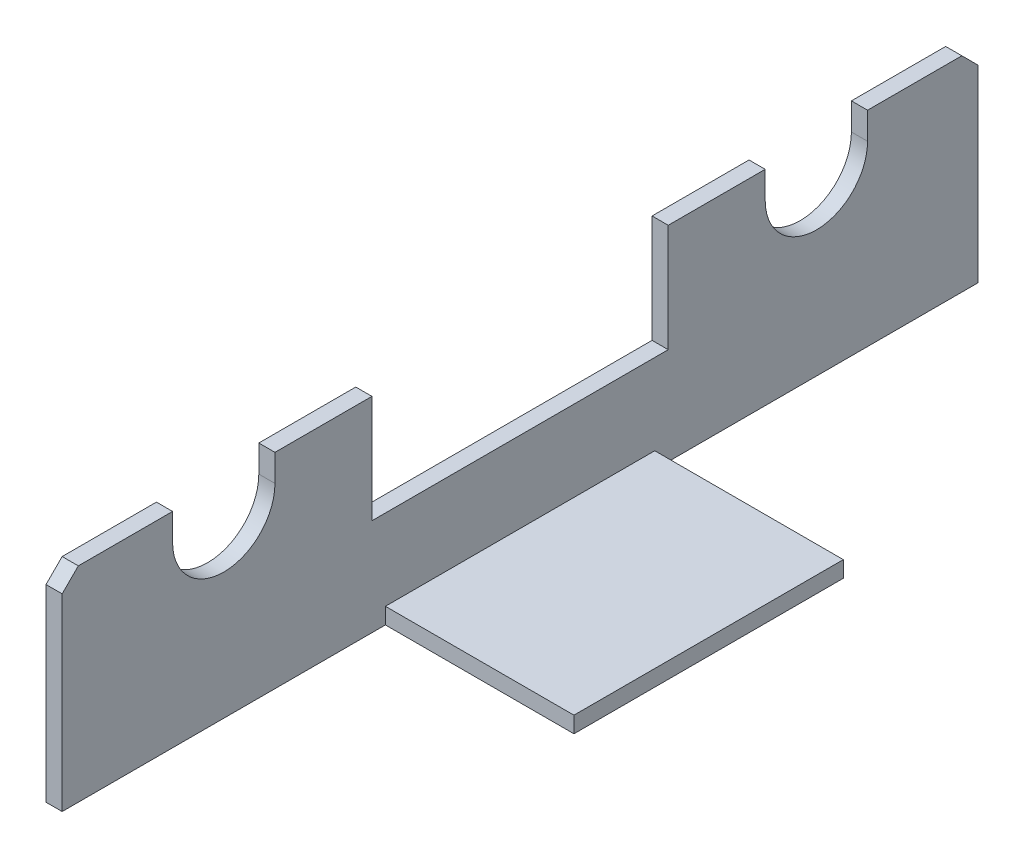
SolidWorks part; units mm, degrees
ref_plane "Alzado" through (0, 0, 0) normal (0, 0, 1) x (1, 0, 0)
ref_plane "Planta" through (0, 0, 0) normal (0, 1, 0) x (1, 0, 0)
ref_plane "Vista lateral" through (0, 0, 0) normal (1, 0, 0) x (0, 0, -1)
sketch "Croquis1" plane through (0, 0, 0) normal (0, 0, 1) x (1, 0, 0)
  line L0 (0, 0) -> (0, 38)
  line L1 (0, 0) -> (38, 0)
  line L2 (3, 3) -> (38, 3)
  line L3 (3, 3) -> (3, 38)
  line L4 (0, 38) -> (3, 38)
  line L5 (38, 3) -> (38, 0)
  dimension "D2" = 38
  dimension "D1" = 3
extrude "Saliente-Extruir1" add sketch "Croquis1" along normal blind 170
sketch "Croquis2" plane through (0, 0, 0) normal (-1, 0, 0) x (0, 0, 1)
  line L0 (170, 33) -> (0, 33) construction
  line L1 (170, 38) -> (170, 0) construction
  line L2 (0, 38) -> (0, 0) construction
  line L3 (170, 3) -> (0, 3) construction
  line L4 (170, 3) -> (0, 3) construction
  line L5 (85, 3) -> (85, 38) construction
  line L6 (170, 38) -> (0, 38) construction
  line L7 (112.5, 18) -> (112.5, 38)
  line L8 (112.5, 58) -> (57.5, 58) construction
  line L9 (112.5, 58) -> (112.5, 18) construction
  line L10 (112.5, 18) -> (57.5, 18)
  line L11 (57.5, 58) -> (57.5, 18) construction
  line L12 (112.5, 58) -> (57.5, 18) construction
  line L13 (112.5, 18) -> (57.5, 58) construction
  line L14 (57.5, 18) -> (57.5, 38)
  line L15 (57.5, 38) -> (112.5, 38)
  line L16 (149.5, 33) -> (149.5, 38)
  line L17 (130.5, 33) -> (130.5, 38)
  line L18 (130.5, 38) -> (149.5, 38)
  line L19 (39.5, 33) -> (39.5, 38)
  line L20 (20.5, 33) -> (20.5, 38)
  line L21 (39.5, 38) -> (20.5, 38)
  circle A0 centre (140, 33) radius 9.5 construction
  circle A1 centre (30, 33) radius 9.5 construction
  arc A2 (149.5, 33) -> (130.5, 33) centre (140, 33) cw
  arc A3 (39.5, 33) -> (20.5, 33) centre (30, 33) cw
  dimension "D2" = 19
  dimension "D1" = 30
  dimension "D3" = 55
  dimension "D4" = 55
  dimension "D5" = 20
  dimension "D6" = 55
extrude "Cortar-Extruir1" cut sketch "Croquis2" against normal up to surface (3 mm away) up to face at (3, 20.5, 85)
chamfer "Chaflán1" distance 3 angle 45 2 edges at (1.5, 38, 170) (1.5, 38, 0)
sketch "Croquis3" plane through (0, 0, 0) normal (0, -1, 0) x (1, 0, 0)
  line L0 (0, 85) -> (38, 85) construction
  line L1 (0, 170) -> (0, 0) construction
  line L2 (38, 170) -> (38, 0) construction
  line L3 (3, 170) -> (3, 0) construction
  line L4 (38, 0) -> (3, 0)
  line L5 (38, 0) -> (38, 60)
  line L6 (38, 60) -> (3, 60)
  line L7 (3, 0) -> (3, 60)
  line L8 (3, 170) -> (3, 0) construction
  line L9 (38, 110) -> (3, 110)
  line L10 (3, 170) -> (3, 110)
  line L11 (38, 170) -> (3, 170)
  line L12 (38, 170) -> (38, 110)
  line M5 (0, 0) -> (38, 0)
  line M6 (38, 0) -> (38, 170)
  line M7 (38, 170) -> (0, 170)
  dimension "D1" = 60
extrude "Cortar-Extruir2" cut sketch "Croquis3" against normal up to surface (3 mm away) contours L10 L9 M7 M6 | L7 L6 M5 M6 region at (20.5, 0, 140) region at (20.5, 0, 30) up to face at (20.5, 3, 85)
